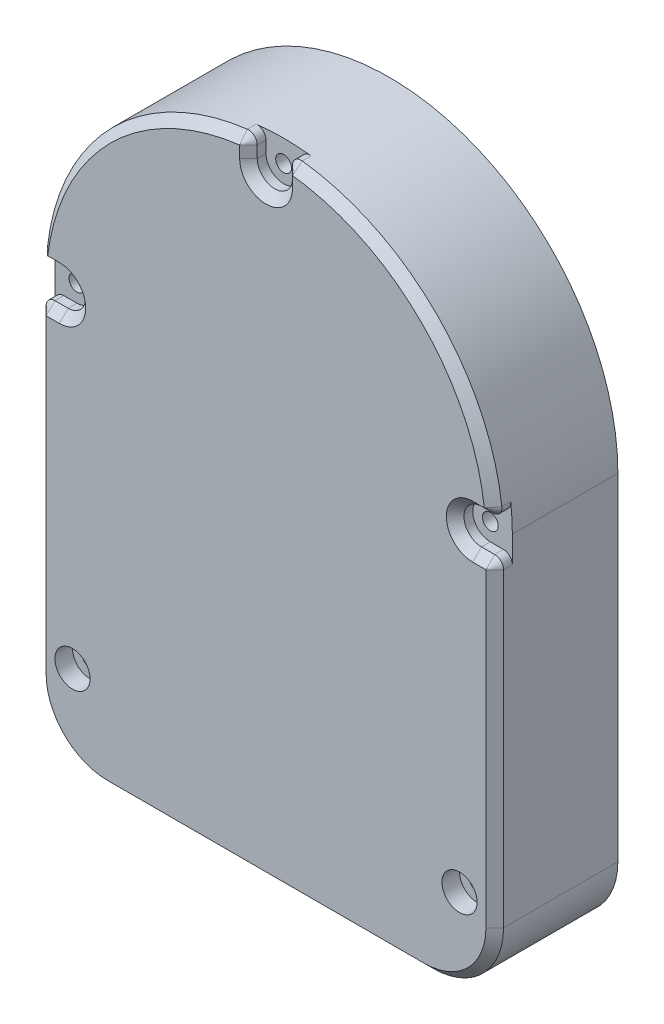
SolidWorks part; units mm, degrees
ref_plane "Спереди" through (0, 0, 0) normal (0, 0, 1) x (1, 0, 0)
ref_plane "Сверху" through (0, 0, 0) normal (0, 1, 0) x (1, 0, 0)
ref_plane "Справа" through (0, 0, 0) normal (1, 0, 0) x (0, 0, -1)
sketch "Эскиз2" plane through (0, 0, 0) normal (0, 0, 1) x (1, 0, 0)
  line L0 (0, 0) -> (0, 0.25)
  line L1 (-26, -10) -> (26, -10) construction
  line L2 (-26, 26.25) -> (26, 26.25)
  line L3 (-26, 26.25) -> (-26, -20)
  line L4 (-26, -20) -> (26, -20)
  line L5 (26, 26.25) -> (26, -20)
  line L6 (0, 26.25) -> (0, -20) construction
  circle A0 centre (0, 26.25) radius 26
  circle A1 centre (0, 26.25) radius 19
  circle A2 centre (-12, -10) radius 2.75
  circle A3 centre (12, -10) radius 2.75
  dimension "D1" = 52
  dimension "D4" = 38
  dimension "D6" = 5.5
  dimension "D2" = 0.25
  dimension "D3" = 20
  dimension "D5" = 10
  dimension "D7" = 24
extrude "Бобышка-Вытянуть1" add sketch "Эскиз2" along normal blind 14 contours A1 L2 A0 | A1 L2 A0 | A0 L3 L4 L5 A3 A2 region at (0, 45.8314, 0) region at (22.5, 25.6686, 0) region at (0, -6.3025, 0)
sketch "Эскиз3" plane through (0, 0, 14) normal (0, 0, 1) x (1, 0, 0)
  circle A0 centre (0, 26.25) radius 21.125
  dimension "D1" = 42.25
extrude "Вырез-Вытянуть1" cut sketch "Эскиз3" against normal blind 12.15
fillet "Скругление1" radius 8 2 edges at (-26, -20, 7) (26, -20, 7)
sketch "Эскиз5" plane through (0, 0, 14) normal (0, 0, 1) x (1, 0, 0)
  line L1 (-18, -20) -> (18, -20) construction
  line L2 (0, 26.25) -> (0, -20) construction
  circle A2 centre (0, 26.25) radius 23.5 construction
  circle A3 centre (0, 26.25) radius 21.125 construction
  circle A4 centre (0, 49.75) radius 0.9
  circle A5 centre (-23.5, 26.25) radius 0.9
  circle A6 centre (0, 2.75) radius 0.9 construction
  circle A7 centre (23.5, 26.25) radius 0.9
  circle A8 centre (-22, -10) radius 0.9
  circle A9 centre (22, -10) radius 0.9
  dimension "D1" = 47
  dimension "D2" = 1.8
  dimension "D6" = 1.8
  dimension "D4" = 10
  dimension "D5" = 44
  dimension "D3" = 4
extrude "Вырез-Вытянуть3" cut sketch "Эскиз5" against normal through all
sketch "Эскиз6" plane through (0, 0, 14) normal (0, 0, 1) x (1, 0, 0)
  circle A0 centre (0, 26.25) radius 19 construction
  circle A1 centre (0, 26.25) radius 21.125
  circle A2 centre (-12, -10) radius 2.75
  circle A3 centre (12, -10) radius 2.75
  circle A4 centre (0, 26.25) radius 21.125 construction
  circle A5 centre (0, 26.25) radius 19 construction
  circle A6 centre (-12, -10) radius 2.75 construction
  circle A7 centre (12, -10) radius 2.75 construction
extrude "Бобышка-Вытянуть2" add sketch "Эскиз6" against normal through all
sketch "Эскиз7" plane through (0, 0, 0) normal (0, 0, -1) x (-1, 0, 0)
  line L0 (-23.5, 21.75) -> (-18.4594, 21.75) construction
  line L1 (-23.5, 21.75) -> (-24, 21.75)
  line L2 (-24, 21.75) -> (-24, -5.5)
  line L3 (-26, 26.25) -> (-26, -12) construction
  line L4 (0, -20) -> (0, -7.7895) construction
  line L5 (18, -20) -> (-18, -20) construction
  line L6 (-22, -5.5) -> (-24, -5.5)
  line L7 (-17.5, -18) -> (17.5, -18)
  line L8 (-17.5, -10) -> (-17.5, -18)
  line L9 (-22, -14.5) -> (-17.5, -18) construction
  line L10 (17.5, -10) -> (17.5, -18)
  line L11 (22, -5.5) -> (24, -5.5)
  line L12 (24, 21.75) -> (24, -5.5)
  line L13 (23.5, 21.75) -> (24, 21.75)
  arc A1 (19, 26.25) -> (-19, 26.25) centre (0, 26.25) ccw
  arc A2 (26, 26.25) -> (-26, 26.25) centre (0, 26.25) ccw construction
  arc A3 (-23.5, 21.75) -> (-19, 26.25) centre (-23.5, 26.25) ccw
  arc A5 (-18.4594, 21.75) -> (0, 7.25) centre (0, 26.25) ccw construction
  arc A6 (-17.5, -10) -> (-22, -5.5) centre (-22, -10) ccw
  arc A7 (-19, 26.25) -> (-18.4594, 21.75) centre (0, 26.25) ccw construction
  arc A8 (-19, 26.25) -> (-23.5, 21.75) centre (-23.5, 26.25) ccw construction
  arc A9 (-22, -14.5) -> (-17.5, -10) centre (-22, -10) ccw construction
  arc A10 (-22, -5.5) -> (-22, -14.5) centre (-22, -10) ccw construction
  arc A11 (17.5, -10) -> (22, -5.5) centre (22, -10) cw
  arc A12 (23.5, 21.75) -> (19, 26.25) centre (23.5, 26.25) cw
  arc A13 (0, 7.25) -> (19, 26.25) centre (0, 26.25) ccw construction
  circle A14 centre (-23.5, 26.25) radius 0.9 construction
  point P30 (0, -18)
  dimension "D1" = 38
  dimension "D4" = 2
  dimension "D5" = 9
  dimension "D3" = 2
extrude "Вырез-Вытянуть4" cut sketch "Эскиз7" against normal blind 13
sketch "Эскиз8" plane through (0, 0, 14) normal (0, 0, 1) x (1, 0, 0)
  line L0 (2, 49.75) -> (2, 52.25)
  line L1 (2, 52.25) -> (-2, 52.25)
  line L2 (-2, 52.25) -> (-2, 49.75)
  line L3 (26, 28.25) -> (23.5, 28.25)
  line L4 (23.5, 24.25) -> (26, 24.25)
  line L5 (26, 24.25) -> (26, 28.25)
  line L6 (2, 0.25) -> (2, 2.75) construction
  line L7 (-2, 2.75) -> (-2, 0.25) construction
  line L8 (-2, 0.25) -> (2, 0.25) construction
  line L9 (-26, 24.25) -> (-23.5, 24.25)
  line L10 (-23.5, 28.25) -> (-26, 28.25)
  line L11 (-26, 28.25) -> (-26, 24.25)
  arc A0 (-2, 49.75) -> (2, 49.75) centre (0, 49.75) ccw
  arc A1 (26, 26.25) -> (-26, 26.25) centre (0, 26.25) ccw construction
  arc A2 (2, 49.75) -> (-2, 49.75) centre (0, 49.75) ccw construction
  arc A3 (23.5, 28.25) -> (23.5, 24.25) centre (23.5, 26.25) ccw
  arc A4 (2, 2.75) -> (-2, 2.75) centre (0, 2.75) ccw construction
  arc A5 (-23.5, 24.25) -> (-23.5, 28.25) centre (-23.5, 26.25) ccw
  circle A6 centre (23.5, 26.25) radius 0.9 construction
  circle A7 centre (-22, -10) radius 2
  circle A8 centre (22, -10) radius 2
  dimension "D1" = 4
  dimension "D3" = 4
  dimension "D4" = 4
  dimension "D2" = 4
extrude "Вырез-Вытянуть5" cut sketch "Эскиз8" against normal offset from surface (2 mm away) 12 up to face at (0, 5.75, 0)
fillet "Скругление2" radius 1 12 edges at (24, -5.5, 6.5) (17.5, -18, 6.5) (-17.5, -18, 6.5) (-24, -5.5, 6.5) (-24, 21.75, 6.5) (24, 21.75, 6.5) (26, 24.25, 13) (25.923, 28.25, 13) (2, 52.173, 13) (-2, 52.173, 13) (-26, 24.25, 13) (-25.923, 28.25, 13)
sketch "Эскиз9" plane through (-26, 0, 0) normal (-1, 0, 0) x (0, 0, 1)
  line L0 (0, 26.25) -> (0, -12) construction
  line L1 (-7.5, 10.375) -> (4.5, 10.375)
  line L2 (-7.5, 10.375) -> (-7.5, 3.875)
  line L3 (-7.5, 3.875) -> (4.5, 3.875)
  line L4 (7.5, 7.375) -> (7.5, 6.875)
  line L5 (-7.5, 10.375) -> (7.5, 3.875) construction
  line L6 (-7.5, 3.875) -> (7.5, 10.375) construction
  arc A0 (7.5, 6.875) -> (4.5, 3.875) centre (4.5, 6.875) cw
  arc A1 (7.5, 7.375) -> (4.5, 10.375) centre (4.5, 7.375) ccw
  point P0 (0, 7.125)
  dimension "D3" = 3
  dimension "D1" = 7.5
  dimension "D2" = 6.5
extrude "Вырез-Вытянуть6" cut sketch "Эскиз9" against normal up to next
chamfer "Фаска1" distance 1 angle 45 40 edges at (0, -18, 13) (-17.2071, -17.7071, 13) (17.2071, -17.7071, 13) (-17.5, -13.5, 13) (17.5, -13.5, 13) (-18.818, -6.818, 13) (18.818, -6.818, 13) (-22.5, -5.5, 13) (22.5, -5.5, 13) (-23.7071, -5.2071, 13) (23.7071, -5.2071, 13) (-24, 8.1364, 13) (24, 8.1364, 13) (-23.7385, 21.447, 13) (23.7385, 21.447, 13) (-20.1765, 23.2161, 13) (20.1765, 23.2161, 13) (0, 45.25, 13) (25.7071, 23.9571, 14) (24.25, 24.25, 14) (26, 5.625, 14) (21.5, 26.25, 14) (23.6569, -17.6569, 14) (24.1597, 28.25, 14) (0, -20, 14) (25.5677, 28.5867, 14) (-23.6569, -17.6569, 14) (18.3848, 44.6348, 14) (-26, 5.625, 14) (2.3367, 51.8177, 14) (-25.7071, 23.9571, 14) (2, 50.4097, 14) (-24.25, 24.25, 14) (0, 47.75, 14) (-21.5, 26.25, 14) (-2, 50.4097, 14) (-24.1597, 28.25, 14) (-2.3367, 51.8177, 14) (-25.5677, 28.5867, 14) (-18.3848, 44.6348, 14)
equation "\"big_bearing_d1\"= 19.9"
equation "\"big_bearing_d2\"= 42"
equation "\"big_bearing_h\"= 11.9"
equation "\"print_offset\"= 0.5"
equation "\"small_bearing_d1\"= 2.9"
equation "\"small_bearing_d2\"= 10"
equation "\"small_bearing_h\"= 4"
equation "\"tube_d\"= 16"
equation "\"small_bearing_distance\"= 2"
equation "\"D1@Эскиз2\"=\"big_bearing_d2\"+5*2"
equation "\"D2@Эскиз2\"=\"print_offset\"/2"
equation "\"D4@Эскиз2\"=\"big_bearing_d2\"-4"
equation "\"D1@Бобышка-Вытянуть1\"=15"
equation "\"D1@Эскиз3\"=\"big_bearing_d2\"+\"print_offset\"/2"
equation "\"D1@Вырез-Вытянуть1\"=\"big_bearing_h\"+\"print_offset\"/2"
equation "\"D6@Эскиз5\"=\"D2@Эскиз5\""
